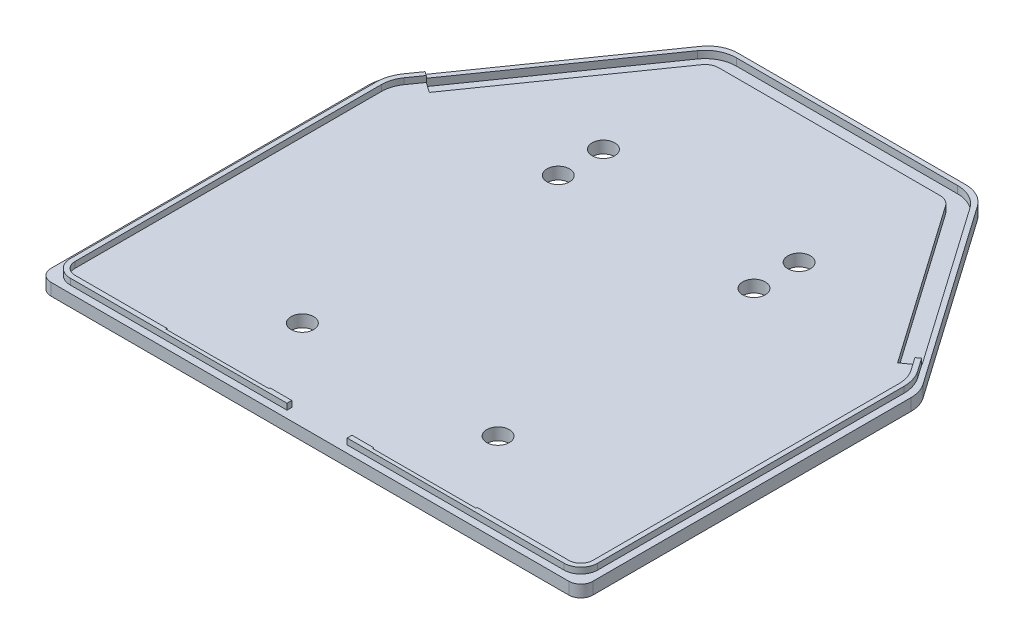
SolidWorks part; units mm, degrees
note: The reader was unsure of these and kept them because the rebuilt part matched: shared geometry of "Sketch5<5>".
ref_plane "Front Plane" through (0, 0, 0) normal (0, 0, 1) x (1, 0, 0)
ref_plane "Top Plane" through (0, 0, 0) normal (0, 1, 0) x (1, 0, 0)
ref_plane "Right Plane" through (0, 0, 0) normal (1, 0, 0) x (0, 0, -1)
sketch "TruckMountingHoles" plane through (0, 0, 0) normal (0, 1, 0) x (1, 0, 0)
  line L0 (-20.6375, 22.225) -> (20.6375, 22.225) construction
  line L1 (-20.6375, -31.75) -> (20.6375, -31.75)
  line L2 (-20.6375, -31.75) -> (-20.6375, 31.75)
  line L3 (-20.6375, 31.75) -> (20.6375, 31.75)
  line L4 (20.6375, -31.75) -> (20.6375, 31.75)
  line L5 (-20.6375, -31.75) -> (20.6375, 31.75) construction
  line L6 (-20.6375, 31.75) -> (20.6375, -31.75) construction
  circle A0 centre (-20.6375, 22.225) radius 2.3813
  circle A1 centre (-20.6375, 31.75) radius 2.3813
  circle A2 centre (20.6375, 31.75) radius 2.3813
  circle A3 centre (20.6375, 22.225) radius 2.3813
  circle A4 centre (20.6375, -31.75) radius 2.3813
  circle A5 centre (-20.6375, -31.75) radius 2.3813
  point P0 (0, 0)
  dimension "D3" = 4.7625
  dimension "D1" = 41.275
  dimension "D2" = 63.5
  dimension "D4" = 53.975
sketch "Sketch2" plane through (0, 0, 0) normal (0, 1, 0) x (1, 0, 0)
  line L1 (-57.15, -50.8) -> (57.15, -50.8)
  line L2 (-57.15, -50.8) -> (-57.15, 50.8)
  line L3 (-57.15, 50.8) -> (57.15, 50.8)
  line L4 (57.15, -50.8) -> (57.15, 50.8)
  line L5 (-57.15, -50.8) -> (57.15, 50.8) construction
  line L6 (-57.15, 50.8) -> (57.15, -50.8) construction
  point P0 (0, 0)
  dimension "D1" = 114.3
  dimension "D2" = 101.6
extrude "Boss-Extrude1" add sketch "Sketch2" along normal blind 2.54
sketch "Sketch3" plane through (0, 2.54, 0) normal (0, 1, 0) x (1, 0, 0)
  line L4 (57.15, 50.8) -> (-57.15, 50.8) construction
  line L5 (-30.1625, -50.8) -> (-11.1125, -50.8)
  line L6 (-30.1625, -50.8) -> (-30.1625, 50.8)
  line L7 (-30.1625, 50.8) -> (-11.1125, 50.8)
  line L13 (-11.1125, -50.8) -> (-11.1125, 50.8)
  line L14 (-30.1625, -50.8) -> (-11.1125, 50.8) construction
  line L15 (-30.1625, 50.8) -> (-11.1125, -50.8) construction
  line L17 (-20.6375, -31.75) -> (-20.6375, 31.75) construction
  line L18 (0, 50.8) -> (0, -50.8) construction
  line L19 (-57.15, -50.8) -> (57.15, -50.8) construction
  line L20 (30.1625, 50.8) -> (11.1125, -50.8) construction
  line L21 (30.1625, -50.8) -> (11.1125, 50.8) construction
  line L22 (11.1125, -50.8) -> (11.1125, 50.8)
  line L23 (30.1625, 50.8) -> (11.1125, 50.8)
  line L24 (30.1625, -50.8) -> (30.1625, 50.8)
  line L25 (30.1625, -50.8) -> (11.1125, -50.8)
  line L26 (-57.15, -50.8) -> (57.15, -50.8)
  line L27 (-30.1625, -12.7) -> (30.1625, -12.7)
  line L28 (-30.1625, -12.7) -> (-30.1625, 12.7)
  line L29 (-30.1625, 12.7) -> (30.1625, 12.7)
  line L30 (30.1625, -12.7) -> (30.1625, 12.7)
  line L31 (-30.1625, -12.7) -> (30.1625, 12.7) construction
  line L32 (-30.1625, 12.7) -> (30.1625, -12.7) construction
  line L33 (-30.1625, 41.7056) -> (-23.7946, 50.8)
  line L35 (-36.2596, 37.4265) -> (-44.9423, 25.0262)
  line L36 (30.1625, 41.7056) -> (23.7946, 50.8)
  point P0 (-20.6375, 0)
  point P17 (20.6375, 0)
  point P18 (0, 0)
  dimension "D1" = 19.05
  dimension "D2" = 25.4
  dimension "D3" = 2.54
extrude "Boss-Extrude2" add sketch "Sketch3" along normal blind 2.54
extrude "Cut-Extrude1" cut sketch "TruckMountingHoles" along normal through all contours A1 | A0 | A4 | A5 | A3 | A2
fillet "Fillet1" radius 2.54 4 edges at (57.15, 1.27, -50.8) (57.15, 1.27, 50.8) (-57.15, 1.27, -50.8) (-57.15, 1.27, 50.8)
sketch "Sketch5" plane through (0, 2.54, 0) normal (0, 1, 0) x (1, 0, 0)
  line L1 (57.15, -48.26) -> (57.15, 48.26) construction
  line L2 (0, 50.8) -> (0, 0) construction
  line L3 (27.305, 63.5) -> (-27.305, 63.5)
  line L4 (23.7946, 50.8) -> (-25.5007, 50.8)
  line L5 (57.15, 20.8769) -> (27.305, 63.5)
  line L6 (-57.15, 20.8769) -> (-27.305, 63.5)
  line L17 (57.15, -48.26) -> (57.15, 48.26)
  line L19 (30.1625, 41.7056) -> (30.1625, 12.7)
  line L20 (30.1625, 12.7) -> (11.1125, 12.7)
  line L21 (11.1125, 12.7) -> (11.1125, 50.8)
  line L22 (11.1125, 50.8) -> (-11.1125, 50.8)
  line L23 (-11.1125, 50.8) -> (-11.1125, 12.7)
  line L24 (-11.1125, 12.7) -> (-30.1625, 12.7)
  line L25 (-30.1625, 12.7) -> (-30.1625, 41.7056)
  line L26 (-23.7946, 50.8) -> (-54.61, 50.8)
  line L27 (-57.15, 48.26) -> (-57.15, -48.26)
  line L28 (-54.61, -50.8) -> (-30.1625, -50.8)
  line L29 (-30.1625, -50.8) -> (-30.1625, -12.7)
  line L30 (-30.1625, -12.7) -> (-11.1125, -12.7)
  line L31 (57.15, -48.26) -> (57.15, 48.26)
  line L51 (30.1625, 41.7056) -> (30.1625, 12.7)
  line L52 (30.1625, 12.7) -> (11.1125, 12.7)
  line L53 (11.1125, 12.7) -> (11.1125, 50.8)
  line L54 (11.1125, 50.8) -> (-11.1125, 50.8)
  line L55 (-11.1125, 50.8) -> (-11.1125, 12.7)
  line L56 (-11.1125, 12.7) -> (-30.1625, 12.7)
  line L57 (-30.1625, 12.7) -> (-30.1625, 41.7056)
  line L58 (-23.7946, 50.8) -> (-54.61, 50.8)
  line L59 (-57.15, 48.26) -> (-57.15, -48.26)
  line L60 (-54.61, -50.8) -> (-30.1625, -50.8)
  line L61 (-30.1625, -50.8) -> (-30.1625, -12.7)
  line L62 (-30.1625, -12.7) -> (-11.1125, -12.7)
  line L71 (54.61, 50.8) -> (23.7946, 50.8)
  line L72 (-30.1625, 41.7056) -> (-23.7946, 50.8)
  line L73 (-30.1625, 41.7056) -> (-23.7946, 50.8)
  line L82 (54.61, 50.8) -> (23.7946, 50.8)
  line L84 (30.1625, -12.7) -> (30.1625, -50.8)
  line L86 (11.1125, -12.7) -> (30.1625, -12.7)
  line L87 (11.1125, -12.7) -> (30.1625, -12.7)
  line L88 (30.1625, -12.7) -> (30.1625, -50.8)
  line L89 (30.1625, -50.8) -> (54.61, -50.8)
  line L90 (30.1625, -50.8) -> (54.61, -50.8)
  line L91 (23.7946, 50.8) -> (30.1625, 41.7056)
  line L92 (23.7946, 50.8) -> (30.1625, 41.7056)
  line L93 (-11.1125, -12.7) -> (-11.1125, -50.8)
  line L94 (-11.1125, -12.7) -> (-11.1125, -50.8)
  line L95 (-11.1125, -50.8) -> (11.1125, -50.8)
  line L96 (-11.1125, -50.8) -> (11.1125, -50.8)
  line L97 (11.1125, -50.8) -> (11.1125, -12.7)
  line L98 (11.1125, -50.8) -> (11.1125, -12.7)
  arc A7 (57.15, 48.26) -> (54.61, 50.8) centre (54.61, 48.26) ccw
  arc A8 (-54.61, 50.8) -> (-57.15, 48.26) centre (-54.61, 48.26) ccw
  arc A13 (-57.15, -48.26) -> (-54.61, -50.8) centre (-54.61, -48.26) ccw
  arc A14 (57.15, 48.26) -> (54.61, 50.8) centre (54.61, 48.26) ccw
  arc A16 (-54.61, 50.8) -> (-57.15, 48.26) centre (-54.61, 48.26) ccw
  arc A17 (-57.15, -48.26) -> (-54.61, -50.8) centre (-54.61, -48.26) ccw
  arc A18 (54.61, -50.8) -> (57.15, -48.26) centre (54.61, -48.26) ccw
  arc A19 (54.61, -50.8) -> (57.15, -48.26) centre (54.61, -48.26) ccw
  dimension "D1" = 0
  dimension "D2" = 12.7
  dimension "D3" = 54.61
extrude "Cut-Extrude3" cut sketch "Sketch5" against normal through all and the other way through all
extrude "Boss-Extrude3" add sketch "Sketch5<5>" against normal up to surface (2.54 mm away) up to face at (20.6375, 0, -29.3687)
sketch "Sketch5<5>" plane through (0, 2.54, 0) normal (0, 1, 0) x (1, 0, 0) same geometry as "Sketch5"
sketch "Sketch6" plane through (0, 2.54, 0) normal (0, 1, 0) x (1, 0, 0)
  line L8 (25.9391, 57.7011) -> (49.4458, 24.13)
  line L9 (-23.3383, 59.055) -> (23.3383, 59.055)
  line L10 (-49.4458, 24.13) -> (-25.9391, 57.7011)
  line L11 (-52.0466, 25.9511) -> (-49.4458, 24.13)
  line L12 (-28.5399, 59.5222) -> (-52.0466, 25.9511)
  line L13 (23.3383, 62.23) -> (-23.3383, 62.23)
  line L14 (52.0466, 25.9511) -> (28.5399, 59.5222)
  line L15 (49.4458, 24.13) -> (52.0466, 25.9511)
  line L16 (25.9391, 57.7011) -> (49.4458, 24.13)
  line L17 (-23.3383, 59.055) -> (23.3383, 59.055)
  line L18 (-49.4458, 24.13) -> (-25.9391, 57.7011)
  line L19 (-52.0466, 25.9511) -> (-49.4458, 24.13)
  line L20 (-28.5399, 59.5222) -> (-52.0466, 25.9511)
  line L21 (23.3383, 62.23) -> (-23.3383, 62.23)
  line L22 (52.0466, 25.9511) -> (28.5399, 59.5222)
  line L23 (49.4458, 24.13) -> (52.0466, 25.9511)
  line L24 (49.3835, 23.7762) -> (52.4004, 25.8887)
  line L25 (25.731, 57.5554) -> (49.3835, 23.7762)
  line L26 (-23.3383, 58.801) -> (23.3383, 58.801)
  line L27 (-49.3835, 23.7762) -> (-25.731, 57.5554)
  line L28 (-52.4004, 25.8887) -> (-49.3835, 23.7762)
  line L29 (-28.748, 59.6679) -> (-52.4004, 25.8887)
  line L30 (23.3383, 62.484) -> (-23.3383, 62.484)
  line L31 (52.4004, 25.8887) -> (28.748, 59.6679)
  line L32 (49.3835, 23.7762) -> (52.4004, 25.8887)
  line L33 (25.731, 57.5554) -> (49.3835, 23.7762)
  line L34 (-23.3383, 58.801) -> (23.3383, 58.801)
  line L35 (-49.3835, 23.7762) -> (-25.731, 57.5554)
  line L36 (-52.4004, 25.8887) -> (-49.3835, 23.7762)
  line L37 (-28.748, 59.6679) -> (-52.4004, 25.8887)
  line L38 (23.3383, 62.484) -> (-23.3383, 62.484)
  line L39 (52.4004, 25.8887) -> (28.748, 59.6679)
  arc A4 (25.9391, 57.7011) -> (23.3383, 59.055) centre (23.3383, 55.88) ccw
  arc A5 (-23.3383, 59.055) -> (-25.9391, 57.7011) centre (-23.3383, 55.88) ccw
  arc A6 (-23.3383, 62.23) -> (-28.5399, 59.5222) centre (-23.3383, 55.88) ccw
  arc A7 (28.5399, 59.5222) -> (23.3383, 62.23) centre (23.3383, 55.88) ccw
  arc A8 (25.9391, 57.7011) -> (23.3383, 59.055) centre (23.3383, 55.88) ccw
  arc A9 (-23.3383, 59.055) -> (-25.9391, 57.7011) centre (-23.3383, 55.88) ccw
  arc A10 (-23.3383, 62.23) -> (-28.5399, 59.5222) centre (-23.3383, 55.88) ccw
  arc A11 (28.5399, 59.5222) -> (23.3383, 62.23) centre (23.3383, 55.88) ccw
  arc A12 (25.731, 57.5554) -> (23.3383, 58.801) centre (23.3383, 55.88) ccw
  arc A13 (-23.3383, 58.801) -> (-25.731, 57.5554) centre (-23.3383, 55.88) ccw
  arc A14 (-23.3383, 62.484) -> (-28.748, 59.6679) centre (-23.3383, 55.88) ccw
  arc A15 (28.748, 59.6679) -> (23.3383, 62.484) centre (23.3383, 55.88) ccw
  arc A16 (25.731, 57.5554) -> (23.3383, 58.801) centre (23.3383, 55.88) ccw
  arc A17 (-23.3383, 58.801) -> (-25.731, 57.5554) centre (-23.3383, 55.88) ccw
  arc A18 (-23.3383, 62.484) -> (-28.748, 59.6679) centre (-23.3383, 55.88) ccw
  arc A19 (28.748, 59.6679) -> (23.3383, 62.484) centre (23.3383, 55.88) ccw
  dimension "D1" = 0
  dimension "D2" = 0
extrude "Cut-Extrude4" cut sketch "Sketch6" against normal offset from surface (1.524 mm away) 0.254 contours A19 L38 A18 L37 L36 L35 A17 L34 A16 L33 L32 L39
fillet "Fillet2" radius 6.35 4 edges at (-57.15, 1.27, -20.8769) (-27.305, 1.27, -63.5) (27.305, 1.27, -63.5) (57.15, 1.27, -20.8769)
sketch "Sketch7" plane through (0, 0, 0) normal (0, -1, 0) x (1, 0, 0)
  line L1 (57.15, 48.26) -> (57.15, -18.8748) construction
  line L2 (56.0016, -22.517) -> (29.201, -60.7922) construction
  point P0 (57.15, -20.8769)
sketch "Sketch8" plane through (0, 2.54, 0) normal (0, 1, 0) x (1, 0, 0)
  line L0 (-11.1125, -48.26) -> (11.1125, -48.26)
  line L14 (-29.201, 60.7922) -> (-56.0016, 22.517)
  line L15 (-57.15, 18.8748) -> (-57.15, -48.26)
  line L16 (-54.61, -50.8) -> (-30.1625, -50.8)
  line L17 (-30.1625, -50.8) -> (-30.1625, -12.7)
  line L18 (-30.1625, -12.7) -> (-11.1125, -12.7)
  line L19 (-11.1125, -12.7) -> (-11.1125, -50.8)
  line L20 (-11.1125, -50.8) -> (11.1125, -50.8)
  line L21 (11.1125, -50.8) -> (11.1125, -12.7)
  line L22 (11.1125, -12.7) -> (30.1625, -12.7)
  line L23 (30.1625, -12.7) -> (30.1625, -50.8)
  line L24 (30.1625, -50.8) -> (54.61, -50.8)
  line L25 (57.15, -48.26) -> (57.15, 18.8748)
  line L26 (56.0016, 22.517) -> (29.201, 60.7922)
  line L27 (23.9994, 63.5) -> (-23.9994, 63.5)
  line L28 (-29.201, 60.7922) -> (-56.0016, 22.517)
  line L29 (-57.15, 18.8748) -> (-57.15, -48.26)
  line L30 (-54.61, -50.8) -> (-30.1625, -50.8)
  line L31 (-30.1625, -50.8) -> (-30.1625, -12.7)
  line L32 (-30.1625, -12.7) -> (-11.1125, -12.7)
  line L33 (-11.1125, -12.7) -> (-11.1125, -50.8)
  line L34 (-11.1125, -50.8) -> (11.1125, -50.8)
  line L35 (11.1125, -50.8) -> (11.1125, -12.7)
  line L36 (11.1125, -12.7) -> (30.1625, -12.7)
  line L37 (30.1625, -12.7) -> (30.1625, -50.8)
  line L38 (30.1625, -50.8) -> (54.61, -50.8)
  line L39 (57.15, -48.26) -> (57.15, 18.8748)
  line L40 (56.0016, 22.517) -> (29.201, 60.7922)
  line L41 (23.9994, 63.5) -> (-23.9994, 63.5)
  arc A6 (-56.0016, 22.517) -> (-57.15, 18.8748) centre (-50.8, 18.8748) ccw
  arc A7 (-57.15, -48.26) -> (-54.61, -50.8) centre (-54.61, -48.26) ccw
  arc A8 (54.61, -50.8) -> (57.15, -48.26) centre (54.61, -48.26) ccw
  arc A9 (57.15, 18.8748) -> (56.0016, 22.517) centre (50.8, 18.8748) ccw
  arc A10 (29.201, 60.7922) -> (23.9994, 63.5) centre (23.9994, 57.15) ccw
  arc A11 (-23.9994, 63.5) -> (-29.201, 60.7922) centre (-23.9994, 57.15) ccw
  arc A12 (-56.0016, 22.517) -> (-57.15, 18.8748) centre (-50.8, 18.8748) ccw
  arc A13 (-57.15, -48.26) -> (-54.61, -50.8) centre (-54.61, -48.26) ccw
  arc A14 (54.61, -50.8) -> (57.15, -48.26) centre (54.61, -48.26) ccw
  arc A15 (57.15, 18.8748) -> (56.0016, 22.517) centre (50.8, 18.8748) ccw
  arc A16 (29.201, 60.7922) -> (23.9994, 63.5) centre (23.9994, 57.15) ccw
  arc A17 (-23.9994, 63.5) -> (-29.201, 60.7922) centre (-23.9994, 57.15) ccw
  line M51 (-11.1125, -12.7) -> (-11.1125, -50.8)
  line M52 (-11.1125, -50.8) -> (11.1125, -50.8)
  line M53 (11.1125, -50.8) -> (11.1125, -12.7)
  dimension "D2" = 2.54
  dimension "D1" = 0
extrude "Boss-Extrude4" add sketch "Sketch8" along normal up to surface (2.54 mm away) contours L0 M51 M52 M53 up to face at (-20.6375, 5.08, 34.1313)
sketch "Sketch9" plane through (0, 0, 50.8) normal (0, 0, 1) x (1, 0, 0)
  line L0 (11.1125, 9.398) -> (5.08, 9.398) construction
  line L1 (11.1125, 9.398) -> (5.08, 9.398)
  line L4 (-6.35, 8.128) -> (-6.35, 5.18)
  line L5 (-5.08, 3.91) -> (5.08, 3.91)
  line L6 (6.35, 5.18) -> (6.35, 8.128)
  line L7 (5.08, 9.398) -> (-5.08, 9.398)
  line L8 (-6.35, 8.128) -> (-6.35, 5.18)
  line L9 (-5.08, 3.91) -> (5.08, 3.91)
  line L10 (6.35, 5.18) -> (6.35, 8.128)
  line L11 (5.08, 9.398) -> (-5.08, 9.398)
  arc A4 (-6.35, 5.18) -> (-5.08, 3.91) centre (-5.08, 5.18) ccw
  arc A5 (5.08, 3.91) -> (6.35, 5.18) centre (5.08, 5.18) ccw
  arc A6 (6.35, 8.128) -> (5.08, 9.398) centre (5.08, 8.128) ccw
  arc A7 (-5.08, 9.398) -> (-6.35, 8.128) centre (-5.08, 8.128) ccw
  arc A8 (-6.35, 5.18) -> (-5.08, 3.91) centre (-5.08, 5.18) ccw
  arc A9 (5.08, 3.91) -> (6.35, 5.18) centre (5.08, 5.18) ccw
  arc A10 (6.35, 8.128) -> (5.08, 9.398) centre (5.08, 8.128) ccw
  arc A11 (-5.08, 9.398) -> (-6.35, 8.128) centre (-5.08, 8.128) ccw
  line M13 (30.1625, 5.08) -> (-30.1625, 5.08)
  dimension "D1" = 0
extrude "Cut-Extrude5" cut sketch "Sketch9" against normal blind 2.54 contours L9 A9 A8 M13
sketch "Sketch10" plane through (0, 5.08, 0) normal (0, 1, 0) x (1, 0, 0)
  line L0 (23.7946, 50.8) -> (11.1125, 50.8) construction
  line L1 (-30.1625, -50.8) -> (30.1625, -50.8)
  line L2 (-30.1625, -50.8) -> (-30.1625, 50.8)
  line L3 (-30.1625, 50.8) -> (30.1625, 50.8)
  line L4 (30.1625, -50.8) -> (30.1625, 50.8)
  line L5 (30.1625, -50.8) -> (30.1625, -12.7) construction
extrude "Cut-Extrude6" cut sketch "Sketch10" against normal up to surface (2.54 mm away) up to face at (0, 2.54, -48.188)
sketch "Sketch11" plane through (0, 2.54, 0) normal (0, 1, 0) x (1, 0, 0)
  line L0 (55.6232, -45.72) -> (55.6232, 18.8767)
  line L1 (54.2919, 23.0988) -> (52.5046, 25.6517)
  line L2 (52.5046, 25.6517) -> (52.5046, 25.6517)
  line L3 (52.5046, 25.6517) -> (51.8805, 25.2146)
  line L4 (51.8805, 25.2146) -> (53.6677, 22.6618)
  line L5 (54.8612, 18.8767) -> (54.8612, -45.72)
  line L6 (52.0645, -48.514) -> (32.7025, -48.514)
  line L7 (32.7025, -48.514) -> (6.604, -48.514)
  line L8 (6.604, -48.514) -> (6.604, -49.276)
  line L9 (6.35, -49.276) -> (32.7025, -49.276)
  line L10 (32.7025, -49.276) -> (52.0645, -49.276)
  line L11 (6.35, -48.26) -> (6.35, -49.53)
  line L12 (32.7025, -48.26) -> (6.35, -48.26)
  line L13 (52.0645, -48.26) -> (32.7025, -48.26)
  line L14 (54.6072, 18.8767) -> (54.6072, -45.72)
  line L15 (51.5267, 25.277) -> (53.4596, 22.5162)
  line L16 (52.4004, 25.8887) -> (51.5267, 25.277)
  line L17 (52.5671, 26.0053) -> (52.4004, 25.8887)
  line L18 (54.5, 23.2445) -> (52.5671, 26.0053)
  line L19 (55.8772, -45.72) -> (55.8772, 18.8767)
  line L20 (32.7025, -49.53) -> (52.0645, -49.53)
  line L21 (6.35, -49.53) -> (32.7025, -49.53)
  line L22 (6.35, -48.26) -> (6.35, -49.53)
  line L23 (32.7025, -48.26) -> (6.35, -48.26)
  line L24 (52.0645, -48.26) -> (32.7025, -48.26)
  line L25 (54.6072, 18.8767) -> (54.6072, -45.72)
  line L26 (51.5267, 25.277) -> (53.4596, 22.5162)
  line L27 (52.4004, 25.8887) -> (51.5267, 25.277)
  line L28 (52.5671, 26.0053) -> (52.4004, 25.8887)
  line L29 (54.5, 23.2445) -> (52.5671, 26.0053)
  line L30 (55.8772, -45.72) -> (55.8772, 18.8767)
  line L31 (32.7025, -49.53) -> (52.0645, -49.53)
  line L32 (6.35, -49.53) -> (32.7025, -49.53)
  line L33 (6.604, -49.276) -> (32.7025, -49.276) construction
  line L34 (10.922, -48.514) -> (10.922, -48.26)
  line L35 (32.7025, -48.26) -> (32.7025, -48.514)
  line L36 (52.5046, 25.6517) -> (52.359, 25.8597)
  ellipse E1 centre (52.0645, -45.72) end of major axis (49.5217, -45.72) minor radius 2.54 (52.0645, -48.26) -> (54.6072, -45.72) ccw
  ellipse E2 centre (52.0645, -45.72) end of major axis (49.5217, -45.72) minor radius 2.54 (52.0645, -48.26) -> (54.6072, -45.72) ccw
  spline S0 degree 1 poles (52.0645, -49.276) (55.6232, -45.72) knots 0 0 1 1 construction
  spline S1 degree 1 poles (55.6232, 18.8767) (54.2919, 23.0988) knots 0 0 1 1 construction
  spline S2 degree 1 poles (53.6677, 22.6618) (54.8612, 18.8767) knots 0 0 1 1 construction
  spline S3 degree 3 poles (-2836.9993, -3958.2131) (-1295.4403, -457.6524) (30.6584, 95.8079) (79.0101, -57.5418) (-1453.2997, -377.494) (-4840.8264, -985.3502) knots -59.933089 -59.933089 -59.933089 -59.933089 0.5 0.5 63.593475 63.593475 63.593475 63.593475 only from (53.4596, 22.5162) to (54.6072, 18.8767)
  spline S4 degree 3 poles (-2118.9766, 4512.304) (1816.7356, -4750.3876) (-1249.4352, 4937.1345) (861.1969, -4903.1885) knots -22.331053 -22.331053 -22.331053 -22.331053 23.333483 23.333483 23.333483 23.333483 only from (55.8772, 18.8767) to (54.5, 23.2445)
  spline S5 degree 3 poles (4827.5092, 1409.1816) (-84.0128, 148.3343) (33.4812, -62.7614) (54.8297, -48.4844) (69.1114, -27.1793) (-141.6562, 90.3739) (-1411.5009, -4818.4889) knots -15.526316 -15.526316 -15.526316 -15.526316 3.534292 3.926991 4.31969 23.353762 23.353762 23.353762 23.353762 only from (52.0645, -49.53) to (55.8772, -45.72)
  spline S6 degree 3 poles (53.4596, 22.5162) (53.833, 21.9828) (54.1179, 21.4051) (54.5093, 20.1637) (54.6072, 19.5278) (54.6072, 18.8767) knots 0 0 0 0 0.5 0.5 1 1 1 1
  spline S7 degree 3 poles (55.8772, 18.8767) (55.8772, 20.4033) (55.3755, 21.9939) (54.5, 23.2445) knots 0 0 0 0 1 1 1 1
  spline S8 degree 3 poles (52.0645, -49.53) (52.5602, -49.53) (53.5624, -49.3319) (54.8297, -48.4844) (55.6787, -47.218) (55.8772, -46.2157) (55.8772, -45.72) knots 3.141593 3.141593 3.141593 3.141593 3.534292 3.926991 4.31969 4.712389 4.712389 4.712389 4.712389
  spline S9 degree 1 poles (52.0645, -48.514) (54.8612, -45.72) knots 0 0 1 1 construction
  spline S10 degree 3 poles (52.0645, -49.276) (52.5272, -49.276) (53.4629, -49.091) (54.6456, -48.3) (55.4378, -47.1182) (55.6232, -46.1827) (55.6232, -45.72) knots 3.141593 3.141593 3.141593 3.141593 3.534292 3.926991 4.31969 4.712389 4.712389 4.712389 4.712389
  spline S11 degree 3 poles (55.6232, 18.8767) (55.6232, 20.3524) (55.1382, 21.89) (54.2919, 23.0988) knots 0 0 0 0 1 1 1 1
  spline S12 degree 3 poles (53.6677, 22.6618) (54.4264, 21.5781) (54.8612, 20.1996) (54.8612, 18.8767) knots 0 0 0 0 1 1 1 1
  spline S13 degree 3 poles (54.8612, -45.72) (54.8612, -46.433) (54.2644, -47.918) (52.7778, -48.514) (52.0645, -48.514) knots 1.570796 1.570796 1.570796 1.570796 2.356194 3.141593 3.141593 3.141593 3.141593
  dimension "D3" = 4.572
  dimension "D1" = 0
  dimension "D2" = 0.254
extrude "Boss-Extrude5" add sketch "Sketch11" along normal blind 1.27 contours L5 S13 L6 L7 L8 L9 L10 S10 L0 S11 L1 L3 L4 S12 | S13 L5 S12 L4 L3 L36 L27 L26 S6 L25 E2 L24 L35 L6 | L7 L34 L23 L22 L9 L8
mirror "Mirror1" about plane through (0, 0, 0) normal (1, 0, 0) of "Boss-Extrude5"
